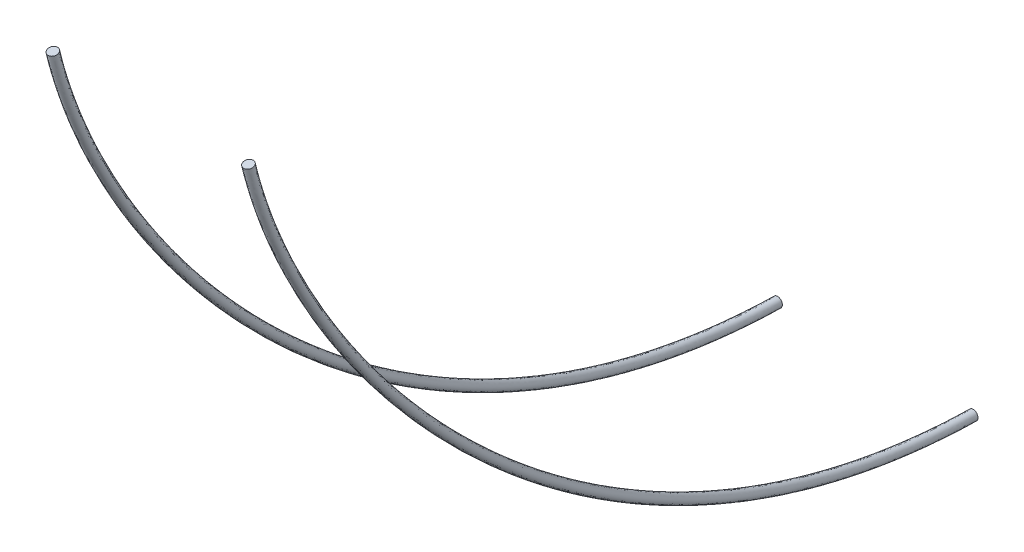
SolidWorks part; units mm, degrees
ref_plane "Front Plane" through (0, 0, 0) normal (0, 0, 1) x (1, 0, 0)
ref_plane "Top Plane" through (0, 0, 0) normal (0, 1, 0) x (1, 0, 0)
ref_plane "Right Plane" through (0, 0, 0) normal (1, 0, 0) x (0, 0, -1)
ref_plane "Plane1" through (20, 0, 0) normal (1, 0, 0) x (0, 0, -1)
sketch "Sketch1" plane through (0, 0, 0) normal (1, 0, 0) x (0, 0, -1)
  line L0 (-82.1841, 46.9914) -> (-72.9142, 8.7525) construction
  line L1 (-77.7014, 28.4999) -> (-86.6669, 65.4829) construction
  line L2 (-82.1841, 46.9914) -> (-91.0752, 44.836) construction
  spline S0 degree 3 poles (-82.1841, 46.9914) (-70.8447, 0.2157) (-12.8113, -69.6585) (65.9644, -71.482) knots 0 0 0 0 1 1 1 1
  point P1 (34.3289, -37.0754)
  point P7 (13.7828, 5.8475)
  point P8 (0, 0)
  point P9 (101.256, -52.1289)
  point P11 (-72.9142, 8.7525)
  point P12 (65.9644, -71.482)
ref_plane "Plane2" through (0, 63.2004, 15.3211) normal (0, 0.9719, 0.2356) x (0, -0.2356, 0.9719)
sketch "Sketch2" plane through (0, 63.2004, 15.3211) normal (0, 0.9719, 0.2356) x (0, -0.2356, 0.9719)
  circle A0 centre (68.7997, 0) radius 1
  dimension "D1" = 2
sweep "Sweep1" add profiles "Sketch2" path "Sketch1"
mirror "Mirror3" about plane through (20, 0, 0) normal (1, 0, 0) of bodies 101
ref_plane "Plane3" through (0, 0, 86.3721) normal (0, 0, 1) x (1, 0, 0)
sketch "Sketch8" plane through (0, 63.2004, 15.3211) normal (0, 0.9719, 0.2356) x (0, -0.2356, 0.9719)
  line L0 (68.7997, 1) -> (68.7997, 39) construction
  line L1 (68.7997, 39) -> (76.8975, 39) construction
  line L2 (76.8975, 39) -> (76.8975, 1) construction
  line L3 (76.8975, 1) -> (68.7997, 1) construction
